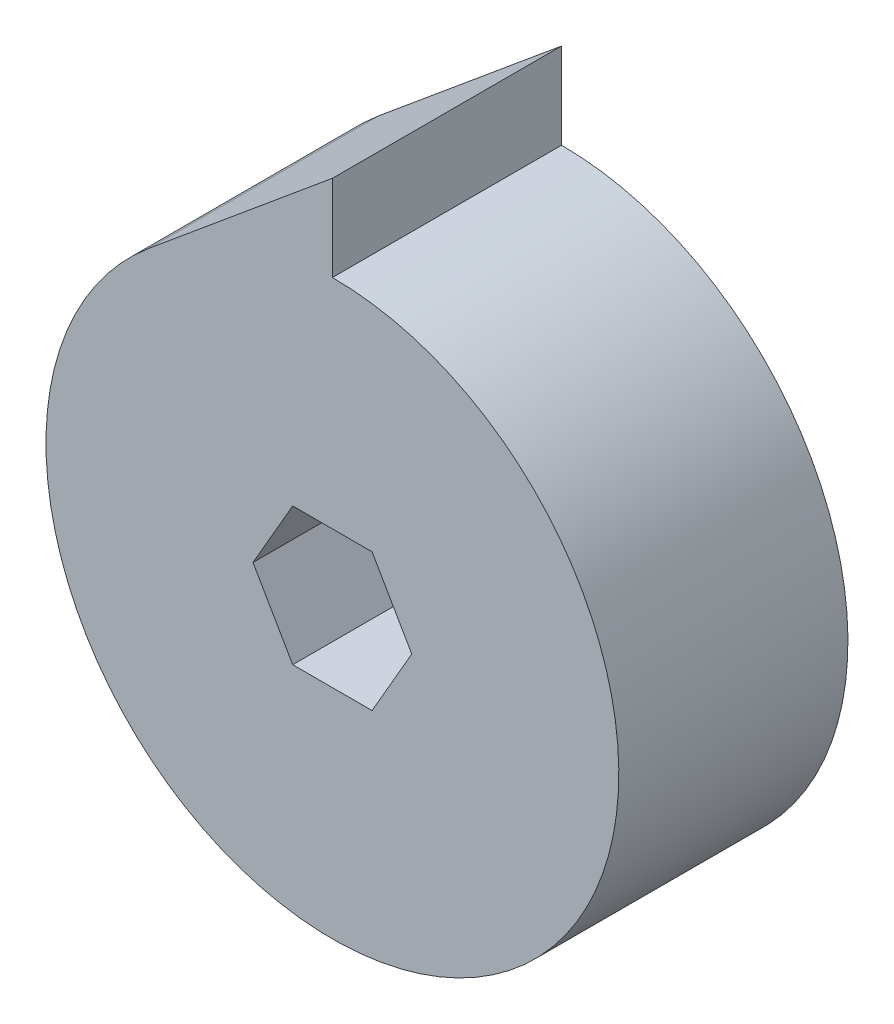
SolidWorks part; units mm, degrees
material "1060 Alloy"
ref_plane "Front Plane" through (0, 0, 0) normal (0, 0, 1) x (1, 0, 0)
ref_plane "Top Plane" through (0, 0, 0) normal (0, 1, 0) x (1, 0, 0)
ref_plane "Right Plane" through (0, 0, 0) normal (1, 0, 0) x (0, 0, -1)
sketch "Sketch3" plane through (0, 0, 0) normal (0, 0, 1) x (1, 0, 0)
  line L0 (0, 25) -> (0, 32.5)
  line L3 (0, 32.5) -> (-15.9743, 19.2308)
  line L6 (6.9282, 0) -> (3.4641, 6)
  line L7 (3.4641, 6) -> (-3.4641, 6)
  line L8 (-3.4641, 6) -> (-6.9282, 0)
  line L9 (-6.9282, 0) -> (-3.4641, -6)
  line L10 (-3.4641, -6) -> (3.4641, -6)
  line L11 (3.4641, -6) -> (6.9282, 0)
  arc A2 (-15.9743, 19.2308) -> (0, 25) centre (0, 0) ccw
  circle A3 centre (0, 0) radius 6 construction
  point P3 (0, 0)
  dimension "D2" = 7.5
  dimension "D1" = 50
  dimension "D3" = 12
extrude "Boss-Extrude1" add sketch "Sketch3" along normal blind 20
